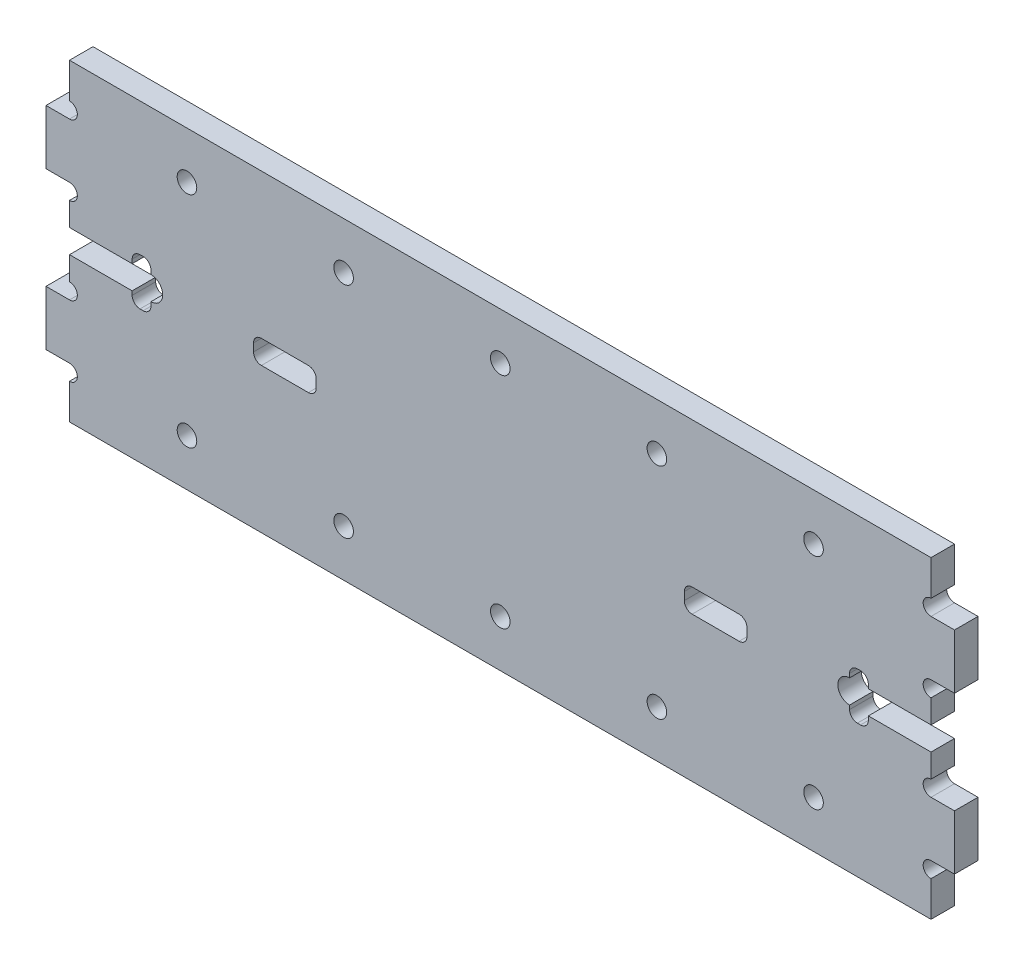
SolidWorks part; units mm, degrees
material "Acrylic (Medium-high impact)"
ref_plane "Front Plane" through (0, 0, 0) normal (0, 0, 1) x (1, 0, 0)
ref_plane "Top Plane" through (0, 0, 0) normal (0, 1, 0) x (1, 0, 0)
ref_plane "Right Plane" through (0, 0, 0) normal (1, 0, 0) x (0, 0, -1)
sketch "Sketch1" plane through (0, 0, 0) normal (0, 0, 1) x (1, 0, 0)
  line L0 (0, 20) -> (0, -20) construction
  line L1 (-55, 20) -> (55, 20)
  line L2 (-55, 20) -> (-55, -20)
  line L3 (-55, -20) -> (55, -20)
  line L4 (55, 20) -> (55, -20)
  line L5 (55, 0) -> (-55, 0) construction
  point P8 (0, 0)
extrude "Boss-Extrude1" add sketch "Sketch1" along normal blind 3
sketch "Sketch2" plane through (0, 0, 3) normal (0, 0, 1) x (1, 0, 0)
  line L0 (-55, 0) -> (55, 0) construction
  line L1 (-55, 20) -> (-55, -20) construction
  line L2 (55, -20) -> (55, 20) construction
  line L3 (55, 0) -> (55, -20) construction
  line L4 (55, 0) -> (55, 20) construction
  line L5 (55, 20) -> (58, 20) construction
  line L6 (58, 20) -> (58, -20) construction
  line L7 (58, -20) -> (55, -20) construction
  line L8 (0, 20) -> (0, -20) construction
  line L9 (55, 20) -> (-55, 20) construction
  line L10 (-55, -20) -> (55, -20) construction
  line L11 (55, -10) -> (58, -10) construction
  line L12 (55, 10) -> (58, 10) construction
  line L13 (58, 10) -> (58, 13.5)
  line L14 (58, 10) -> (58, 6.5)
  line L15 (58, 6.5) -> (55, 6.5)
  line L16 (55, 6.5) -> (55, 13.5)
  line L17 (55, 13.5) -> (58, 13.5)
  line L18 (55, -10) -> (55, -6.5)
  line L19 (55, -6.5) -> (58, -6.5)
  line L20 (58, -6.5) -> (58, -13.5)
  line L21 (58, -13.5) -> (55, -13.5)
  line L22 (55, -13.5) -> (55, -10)
  line L23 (-55, 6.5) -> (-55, 13.5)
  line L24 (-55, -13.5) -> (-55, -10)
  line L25 (-55, -10) -> (-55, -6.5)
  line L26 (-55, 10) -> (-58, 10) construction
  line L27 (-55, -10) -> (-58, -10) construction
  line L28 (-58, -20) -> (-55, -20) construction
  line L29 (-58, 20) -> (-58, -20) construction
  line L30 (-55, 20) -> (-58, 20) construction
  line L31 (-58, -13.5) -> (-55, -13.5)
  line L32 (-58, -6.5) -> (-58, -13.5)
  line L33 (-55, -6.5) -> (-58, -6.5)
  line L34 (-55, 13.5) -> (-58, 13.5)
  line L35 (-58, 6.5) -> (-55, 6.5)
  line L36 (-58, 10) -> (-58, 6.5)
  line L37 (-58, 10) -> (-58, 13.5)
extrude "Boss-Extrude2" add sketch "Sketch2" against normal blind 3
sketch "Sketch3" plane through (0, 0, 3) normal (0, 0, 1) x (1, 0, 0)
  line L0 (-55, 0) -> (55, 0) construction
  line L1 (-55, 6.5) -> (-55, -6.5) construction
  line L2 (55, -6.5) -> (55, 6.5) construction
  line L3 (-55, 13.5) -> (-55, 14.5) construction
  line L4 (-55, 20) -> (-55, 13.5) construction
  line L5 (-55, 14.5) -> (55, 14.5) construction
  line L6 (55, 13.5) -> (55, 20) construction
  line L7 (55, 14.5) -> (55, 5.5) construction
  line L8 (55, 5.5) -> (-55, 5.5) construction
  line L9 (-55, -6.5) -> (-55, -5.5) construction
  line L10 (-55, -5.5) -> (55, -5.5) construction
  line L11 (55, -5.5) -> (55, -14.5) construction
  line L12 (55, -20) -> (55, -13.5) construction
  line L13 (55, -14.5) -> (-55, -14.5) construction
  line L14 (-55, -13.5) -> (-55, -20) construction
  circle A1 centre (-55, 14.5) radius 1
  circle A2 centre (-55, 5.5) radius 1
  circle A3 centre (-55, -5.5) radius 1
  circle A4 centre (-55, -14.5) radius 1
  circle A5 centre (55, 14.5) radius 1
  circle A6 centre (55, 5.5) radius 1
  circle A7 centre (55, -5.5) radius 1
  circle A8 centre (55, -14.5) radius 1
  line M2 (-55, 20) -> (-55, 13.5)
  line M6 (-55, 6.5) -> (-55, -6.5)
  line M10 (-55, -13.5) -> (-55, -20)
  line M12 (55, -20) -> (55, -13.5)
  line M16 (55, -6.5) -> (55, 6.5)
  line M20 (55, 13.5) -> (55, 20)
extrude "Cut-Extrude1" cut sketch "Sketch3" against normal blind 3 contours A4 M10 | A3 M6 | A2 M6 | A1 M2 | A7 M16 | A8 M12 | A6 M16 | A5 M20 region at (-54.5756, 14.5, 3) region at (-54.5756, 5.5, 3) region at (-54.5756, -5.5, 3) region at (-54.5756, -14.5, 3) region at (54.5756, 14.5, 3) region at (54.5756, -5.5, 3) region at (54.5756, 5.5, 3) region at (54.5756, -14.5, 3)
sketch "Sketch4" plane through (0, 0, 3) normal (0, 0, 1) x (1, 0, 0)
  line L0 (-55, 0) -> (55, 0) construction
  line L1 (-55, 4.5) -> (-55, -4.5) construction
  line L2 (55, -4.5) -> (55, 4.5) construction
  line L3 (55, 0) -> (55, -1.5) construction
  line L4 (55, -1.5) -> (-55, -1.5) construction
  line L5 (-55, -1.5) -> (-55, 1.5) construction
  line L6 (-55, 1.5) -> (55, 1.5) construction
  line L7 (55, 1.5) -> (47, 1.5) construction
  line L8 (47, 20) -> (47, -20) construction
  line L9 (55, 20) -> (-55, 20) construction
  line L10 (-55, -20) -> (55, -20) construction
  line L11 (-55, 1.5) -> (-47, 1.5) construction
  line L12 (-47, 20) -> (-47, -20) construction
  line L13 (-47, 20) -> (-44.6, 20) construction
  line L14 (-44.6, 20) -> (-44.6, -20) construction
  line L15 (47, 20) -> (44.6, 20) construction
  line L16 (44.6, 20) -> (44.6, -20) construction
  line L17 (55, 1.5) -> (55, 3) construction
  line L18 (55, 3) -> (-55, 3) construction
  line L19 (-55, 3) -> (-55, -3) construction
  line L20 (-55, -3) -> (55, -3) construction
  line L21 (-44.6, 0) -> (-43.1, 0) construction
  line L22 (44.6, 0) -> (43.1, 0) construction
  line L24 (-55, 1.5) -> (-47, 1.5)
  line L25 (-55, 1.5) -> (-55, -1.5)
  line L26 (-55, -1.5) -> (-47, -1.5)
  line L27 (-47, 1.5) -> (-47, -1.5)
  line L28 (-47, 3) -> (-44.6, 3)
  line L29 (-47, 3) -> (-47, -3)
  line L30 (-47, -3) -> (-44.6, -3)
  line L31 (-44.6, 3) -> (-44.6, -3)
  line L32 (44.6, 3) -> (47, 3)
  line L33 (44.6, 3) -> (44.6, -3)
  line L34 (44.6, -3) -> (47, -3)
  line L35 (47, 3) -> (47, -3)
  line L36 (47, 1.5) -> (55, 1.5)
  line L37 (47, 1.5) -> (47, -1.5)
  line L38 (47, -1.5) -> (55, -1.5)
  line L39 (55, 1.5) -> (55, -1.5)
  arc A0 (44.6, 1.5) -> (44.6, -1.5) centre (44.6, 0) ccw
  arc A1 (-44.6, 1.5) -> (-44.6, -1.5) centre (-44.6, 0) cw
  line M10 (-55, 4.5) -> (-55, -4.5)
  line M24 (55, -4.5) -> (55, 4.5)
extrude "Cut-Extrude2" cut sketch "Sketch4" against normal blind 3 contours L27 L24 L26 M10 | L31 L28 L29 L27 L30 | A1 L31 | L35 L32 L33 L34 | L33 A0 | L35 L38 L36 M24 region at (-51, 0, 3) region at (-45.8, 0, 3) region at (-43.9634, 0, 3) region at (45.8, 0, 3) region at (43.9634, 0, 3) region at (51, 0, 3)
fillet "Fillet6" radius 1 8 edges at (-44.6, 3, 1.5) (-47, 3, 1.5) (-44.6, -3, 1.5) (-47, -3, 1.5) (47, 3, 1.5) (44.6, 3, 1.5) (47, -3, 1.5) (44.6, -3, 1.5)
sketch "Sketch5" plane through (0, 0, 3) normal (0, 0, 1) x (1, 0, 0)
  line L0 (-55, -1.5) -> (-55, 1.5) construction
  line L1 (55, -1.5) -> (55, 1.5) construction
  line L2 (-55, 0) -> (0, 0) construction
  line L3 (0, 0) -> (55, 0) construction
  line L4 (-27.5, 0) -> (-27.5, 1.5) construction
  line L5 (-27.5, 1.5) -> (-23.5, 1.5) construction
  line L6 (-23.5, 1.5) -> (-23.5, -1.5) construction
  line L7 (-23.5, -1.5) -> (-31.5, -1.5) construction
  line L8 (-31.5, -1.5) -> (-31.5, 1.5) construction
  line L9 (-31.5, 1.5) -> (-27.5, 1.5) construction
  line L10 (27.5, 0) -> (27.5, 1.5) construction
  line L11 (27.5, 1.5) -> (31.5, 1.5) construction
  line L12 (31.5, 1.5) -> (31.5, -1.5) construction
  line L13 (31.5, -1.5) -> (23.5, -1.5) construction
  line L14 (23.5, -1.5) -> (23.5, 1.5) construction
  line L15 (23.5, 1.5) -> (27.5, 1.5) construction
  line L17 (-31.5, 1.5) -> (-23.5, 1.5)
  line L18 (-31.5, 1.5) -> (-31.5, -1.5)
  line L19 (-31.5, -1.5) -> (-23.5, -1.5)
  line L20 (-23.5, 1.5) -> (-23.5, -1.5)
  line L21 (23.5, 1.5) -> (31.5, 1.5)
  line L22 (23.5, 1.5) -> (23.5, -1.5)
  line L23 (23.5, -1.5) -> (31.5, -1.5)
  line L24 (31.5, 1.5) -> (31.5, -1.5)
extrude "Cut-Extrude3" cut sketch "Sketch5" against normal blind 10
fillet "Fillet7" radius 1 8 edges at (-31.5, -1.5, 1.5) (-31.5, 1.5, 1.5) (-23.5, 1.5, 1.5) (23.5, -1.5, 1.5) (23.5, 1.5, 1.5) (31.5, 1.5, 1.5) (31.5, -1.5, 1.5) (-23.5, -1.5, 1.5)
sketch "Sketch6" plane through (0, 0, 3) normal (0, 0, 1) x (1, 0, 0)
  line L0 (0, 0) -> (0, 20) construction
  line L1 (55, 20) -> (-55, 20) construction
  line L2 (0, 20) -> (0, 14) construction
  line L3 (0, 0) -> (0, -20) construction
  line L4 (-55, -20) -> (55, -20) construction
  line L5 (0, -20) -> (0, -14) construction
  circle A0 centre (0, 14) radius 1.25
  circle A1 centre (0, -14) radius 1.25
  circle A2 centre (20, -14) radius 1.25
  circle A3 centre (20, 14) radius 1.25
  circle A4 centre (40, -14) radius 1.25
  circle A5 centre (40, 14) radius 1.25
  circle A6 centre (-20, -14) radius 1.25
  circle A7 centre (-20, 14) radius 1.25
  circle A8 centre (-40, -14) radius 1.25
  circle A9 centre (-40, 14) radius 1.25
  dimension "D1" = 3
  dimension "D2" = 3
extrude "Cut-Extrude4" cut sketch "Sketch6" against normal through all contours A8 | A6 | A1 | A2 | A4 | A5 | A3 | A0 | A7 | A9 region at (0, 14, 3) region at (0, -14, 3) region at (20, -14, 3) region at (20, 14, 3) region at (40, -14, 3) region at (40, 14, 3) region at (-20, -14, 3) region at (-20, 14, 3) region at (-40, -14, 3) region at (-40, 14, 3)
